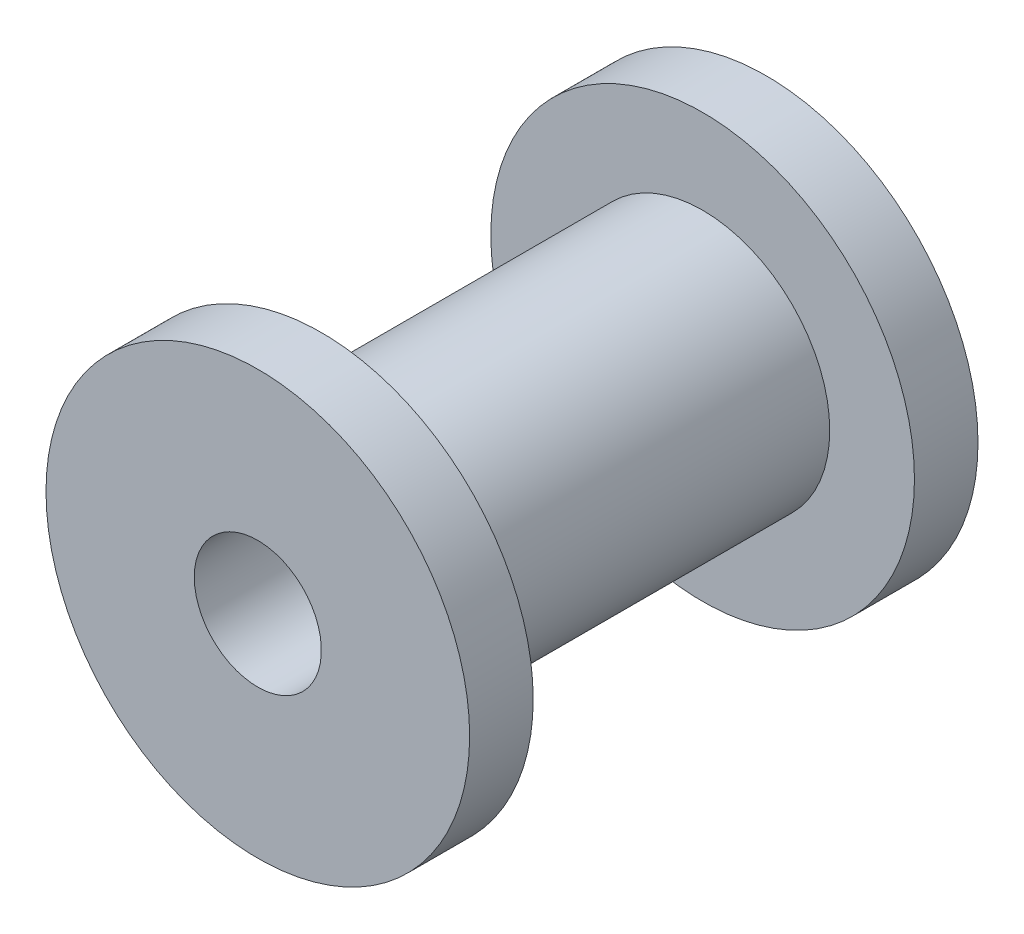
SolidWorks part; units mm, degrees
ref_plane "前视" through (0, 0, 0) normal (0, 0, 1) x (1, 0, 0)
ref_plane "上视" through (0, 0, 0) normal (0, 1, 0) x (1, 0, 0)
ref_plane "右视" through (0, 0, 0) normal (1, 0, 0) x (0, 0, -1)
sketch "草图1" plane through (0, 0, 0) normal (0, 0, 1) x (1, 0, 0)
  circle A0 centre (0, 0) radius 3
  dimension "D1" = 6
extrude "凸台-拉伸1" add sketch "草图1" along normal blind 4.5 and the other way blind 4.5
sketch "草图2" plane through (0, 0, 4.5) normal (0, 0, 1) x (1, 0, 0)
  circle A0 centre (0, 0) radius 5
  dimension "D1" = 10
extrude "凸台-拉伸2" add sketch "草图2" along normal blind 1.5
sketch "草图3" plane through (0, 0, -4.5) normal (0, 0, -1) x (-1, 0, 0)
  circle A0 centre (0, 0) radius 5
  dimension "D1" = 10
extrude "凸台-拉伸3" add sketch "草图3" along normal blind 1.5
sketch "草图4" plane through (0, 0, -6) normal (0, 0, -1) x (-1, 0, 0)
  circle A0 centre (0, 0) radius 1.5
  dimension "D1" = 3
extrude "切除-拉伸1" cut sketch "草图4" against normal through all
